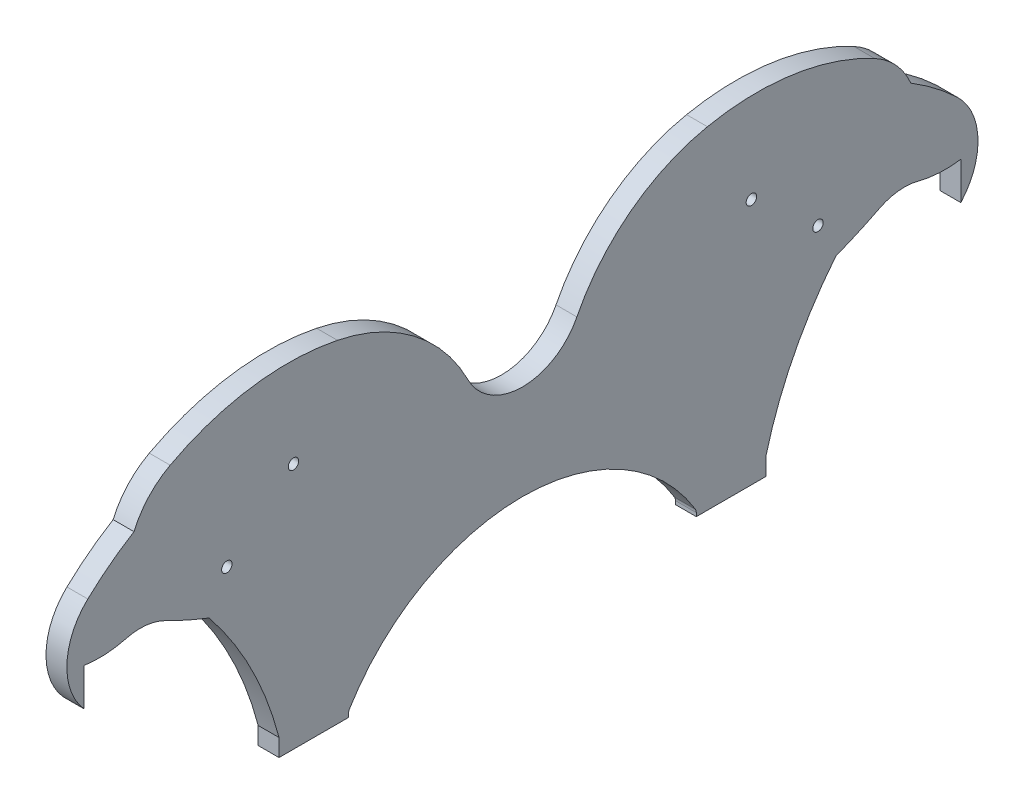
SolidWorks part; units mm, degrees
material "1060 Alloy"
ref_plane "Front Plane" through (0, 0, 0) normal (0, 0, 1) x (1, 0, 0)
ref_plane "Top Plane" through (0, 0, 0) normal (0, 1, 0) x (1, 0, 0)
ref_plane "Right Plane" through (0, 0, 0) normal (1, 0, 0) x (0, 0, -1)
sketch "Sketch1" plane through (0, 0, 0) normal (1, 0, 0) x (0, 0, -1)
  line L10 (196.0788, 40.1801) -> (196.0788, 50.9794)
  line L13 (70, 57.3045) -> (70, 29.9986)
  line L14 (200.4789, 62.5265) -> (174.1246, 31.1187) construction
  line L15 (200.4789, 62.5265) -> (139.1953, 113.9495) construction
  line L16 (174.1246, 31.1187) -> (112.8411, 82.5417) construction
  line L17 (139.1953, 113.9495) -> (112.8411, 82.5417) construction
  line L18 (176.4492, 37.0005) -> (197.0184, 61.514) construction
  line L19 (197.0184, 61.514) -> (166.3767, 87.2255) construction
  line L20 (145.8075, 62.7121) -> (176.4492, 37.0005) construction
  line L21 (186.7338, 49.2573) -> (126.9824, 99.3947) construction
  line L24 (70, 57.3045) -> (59.5071, 57.3045) construction
  line L28 (140, -0.0014) -> (140, 5)
  line L34 (109.9264, 29.9986) -> (27.8485, 29.9986) construction
  line L35 (109.9264, 35.9986) -> (27.8485, 35.9986) construction
  line L36 (135.0961, 75.6162) -> (155.3963, 58.5823) construction
  line L40 (-442.2853, 301.5924) -> (95.3985, 301.5924) construction
  line L41 (135.0961, 75.6162) -> (152.13, 95.9164) construction
  line L42 (155.3963, 58.5823) -> (172.4301, 78.8825) construction
  line L43 (140, -0.0014) -> (120, -0.0014)
  line L44 (152.13, 95.9164) -> (172.4301, 78.8825) construction
  line L56 (120, 1) -> (120, -0.0014)
  line L63 (174.6584, 98) -> (-14.1241, 98) construction
  circle A1 centre (155, 54.9986) radius 1.5
  circle A3 centre (135.8489, 71.0683) radius 1.5
  circle A4 centre (155, 54.9986) radius 3 construction
  circle A5 centre (135.8489, 71.0683) radius 3 construction
  arc A8 (171.3053, 88.4772) -> (181.7122, 77.1302) centre (160.3308, 67.9662) cw
  arc A9 (171.3053, 88.4772) -> (123.201, 95.5334) centre (137.4559, 25.2139) ccw
  arc A10 (181.7122, 77.1302) -> (194.9977, 66.999) centre (140.2642, 9.0009) cw
  arc A15 (194.9977, 66.999) -> (196.0788, 40.1801) centre (181.8212, 53.0366) cw
  arc A16 (160.1441, 44.845) -> (140, 5) centre (242.045, -21.5756) ccw
  arc A17 (123.201, 95.5334) -> (85.6553, 66.9263) centre (133.9569, 42.4745) ccw
  arc A21 (196.0788, 50.9794) -> (183.9392, 51.6401) centre (191.6203, 80.9134) cw
  arc A31 (85.6553, 66.9263) -> (70, 57.3045) centre (70, 74.8516) cw
  arc A44 (120, 1) -> (119.7092, 2.0386) centre (118, 1) ccw
  arc A45 (119.7092, 2.0386) -> (70, 29.9986) centre (70.0008, -28.1681) ccw
  arc A47 (183.9392, 51.6401) -> (172.6156, 50.4177) centre (179.881, 36.174) ccw
  arc A48 (172.6156, 50.4177) -> (160.1441, 44.845) centre (112.2865, 168.69) cw
  point P0 (0, 0)
  dimension "D8" = 120
  dimension "D11" = 55
  dimension "D21" = 40
  dimension "D18" = 6
  dimension "D49" = 30
  dimension "D52" = 26.5
  dimension "D53" = 3
  dimension "D4" = 25
  dimension "D6" = 98
  dimension "D7" = 15
  dimension "D9" = 50
  dimension "D19" = 40
  dimension "D20" = 30
  dimension "D26" = 3
  dimension "D27" = 2
  dimension "D34" = 6
  dimension "D50" = 3.5
  dimension "D51" = 26.5
extrude "Boss-Extrude1" add sketch "Sketch1" along normal blind 6
hole_wizard "Tap Drill for M3 Tap1" positions "Sketch3" profile "Sketch2" hole size "M3" standard "ISO"
sketch "Sketch3" plane through (0, -0.0014, 0) normal (0, -1, 0) x (-1, 0, 0)
  line L2 (-6, 120) -> (0, 120) construction
  line L3 (-6, 120) -> (-6, 140) construction
  point P2 (-3, 130)
  dimension "D1" = 3
  dimension "D3" = 10
sketch "Sketch2" plane through (3, -0.0014, -130) normal (1, 0, 0) x (0, 0, -1)
  line L0 (0, 0) -> (0, 10.7511)
  line L1 (0, 10.7511) -> (1.25, 10)
  line L2 (1.25, 10) -> (1.25, 0)
  line L5 (1.25, 0) -> (0, 0)
  line L10 (0, 10.7511) -> (-1.25, 10) construction
  line L11 (0, -6.35) -> (0, 107.95) construction
  dimension "Hole Dia." = 2.5
  dimension "Hole Depth" = 10
  dimension "Drill Angle" = 118
mirror "Mirror1" about plane through (6, 57.3045, -70) normal (0, 0, -1) of "Tap Drill for M3 Tap1", "Boss-Extrude1"
equation "\"ˇ35\"=76.24"
